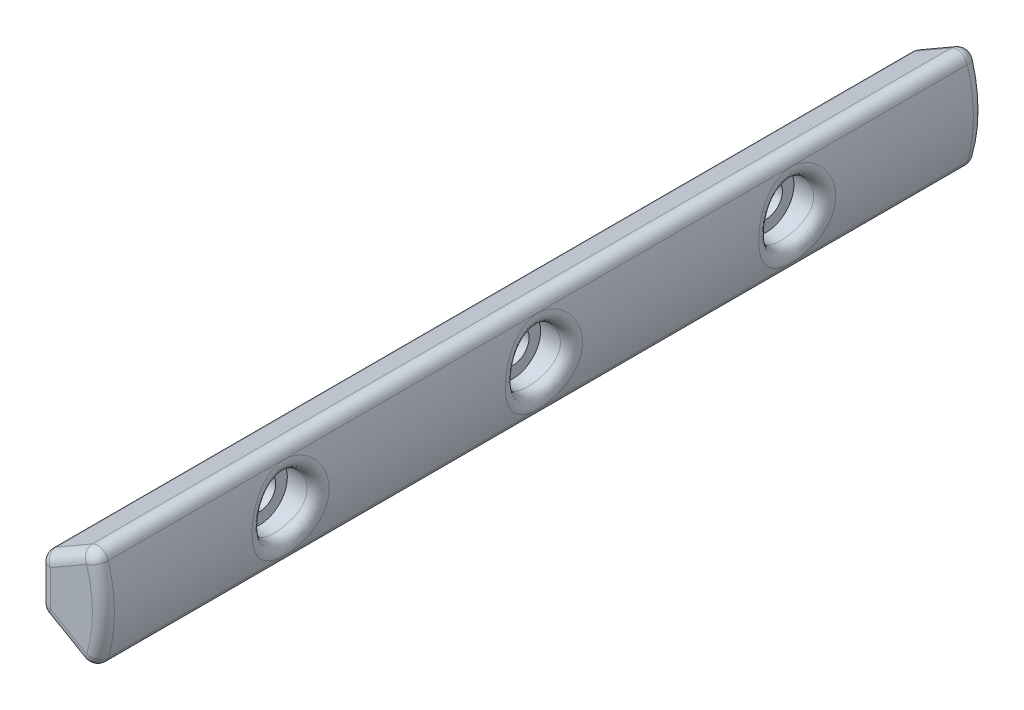
SolidWorks part; units mm, degrees
ref_plane "Front" through (0, 0, 0) normal (0, 0, 1) x (1, 0, 0)
ref_plane "Top" through (0, 0, 0) normal (0, 1, 0) x (1, 0, 0)
ref_plane "Right" through (0, 0, 0) normal (1, 0, 0) x (0, 0, -1)
sketch "Sketch1" plane through (0, 0, 0) normal (0, 0, 1) x (1, 0, 0)
  line L0 (-1.9532, 2.2057) -> (-1.9532, -2.2057)
  line L5 (-5.7735, 0) -> (2.8868, -5)
  line L12 (2.8868, -5) -> (2.8868, 5)
  line L13 (2.8868, 5) -> (-5.7735, 0)
  line L14 (3.8468, 0) -> (-1.9532, 0) construction
  circle A4 centre (0, 0) radius 2.8868 construction
  circle A5 centre (-9.6532, 0) radius 13.5
  dimension "D3" = 27
  dimension "D1" = 10
  dimension "D2" = 5.8
extrude "Boss-Extrude1" add sketch "Sketch1" along normal blind 40 and the other way blind 40 contours L12 L13 L0 L5 | L12 A5 region at (0.7796, 0, 0) region at (3.272, 0, 0)
sketch "Sketch2" plane through (-1.9532, 0, 0) normal (-1, 0, 0) x (0, 0, 1)
  circle A4 centre (0, 0) radius 1.45
  circle A5 centre (-23, 0) radius 1.45
  circle A6 centre (23, 0) radius 1.45
  dimension "D2" = 2.9
  dimension "D1" = 2.9
  dimension "D3" = 2.9
  dimension "D4" = 23
  dimension "D5" = 23
extrude "Cut-Extrude1" cut sketch "Sketch2" against normal through all
sketch "Croquis3" plane through (-1.9532, 0, 0) normal (1, 0, 0) x (0, 0, -1)
  circle A4 centre (-23, 0) radius 2.5
  circle A5 centre (0, 0) radius 2.5
  circle A6 centre (23, 0) radius 2.5
  dimension "D1" = 5
  dimension "D2" = 5
  dimension "D3" = 5
extrude "Cortar-Extruir2" cut sketch "Croquis3" along normal blind 3 from offset 3
fillet "Redondeo1" radius 1 15 edges at (3.8468, 0, -40) (0.4668, 3.6028, -40) (-1.9532, 0, -40) (0.4668, -3.6028, -40) (-1.9532, 0, 40) (0.4668, 3.6028, 40) (3.8468, 0, 40) (0.4668, -3.6028, 40) (3.8365, 0.5273, -20.5562) (3.8365, 0.5273, 2.4438) (3.8365, 0.5273, 25.4438) (-1.9532, 2.2057, 0) (-1.9532, -2.2057, 0) (2.8868, -5, 0) (2.8868, 5, 0)
